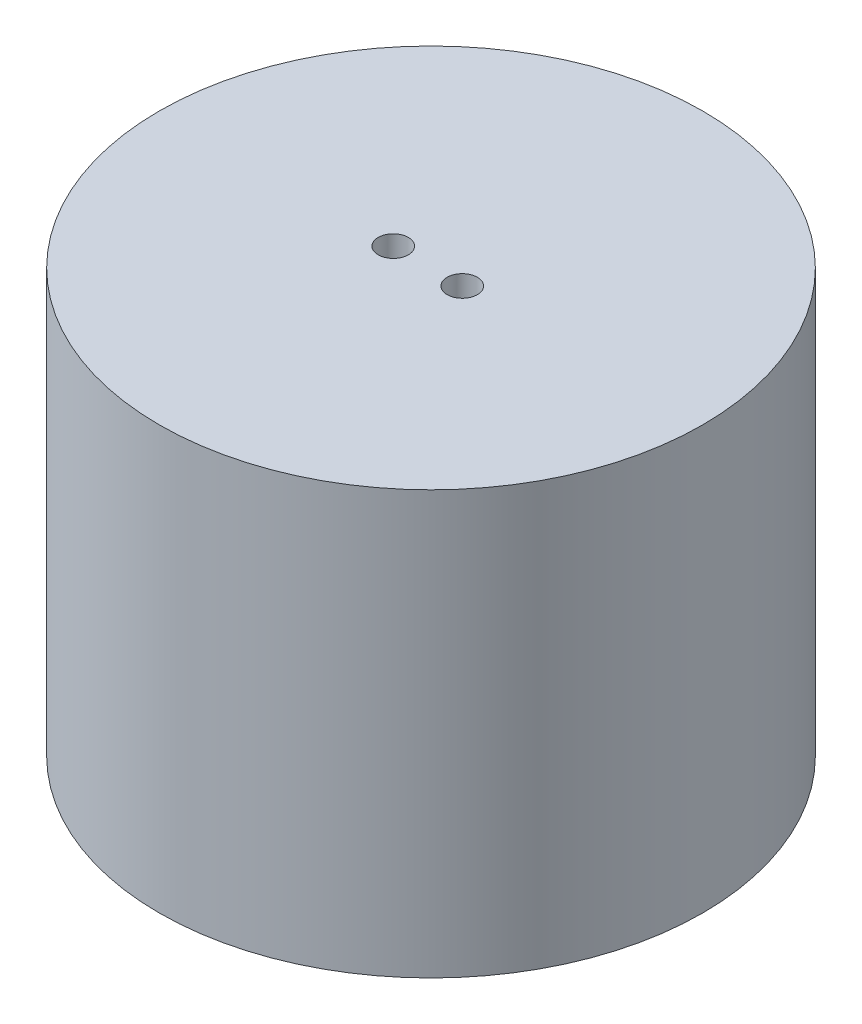
SolidWorks part; units mm, degrees
ref_plane "Front Plane" through (0, 0, 0) normal (0, 0, 1) x (1, 0, 0)
ref_plane "Top Plane" through (0, 0, 0) normal (0, 1, 0) x (1, 0, 0)
ref_plane "Right Plane" through (0, 0, 0) normal (1, 0, 0) x (0, 0, -1)
sketch "Sketch1" plane through (0, 0, 0) normal (0, 1, 0) x (1, 0, 0)
  circle A0 centre (0, 0) radius 7.75
  circle A1 centre (0, 0) radius 9
extrude "Boss-Extrude1" add sketch "Sketch1" along normal blind 4
sketch "Sketch2" plane through (0, 4, 0) normal (0, 1, 0) x (1, 0, 0)
  circle A0 centre (0, 0) radius 9
  circle A1 centre (0, 0) radius 6
extrude "Boss-Extrude2" add sketch "Sketch2" along normal blind 9
thread "Thread2" pitch 1 method cut trim with start face yes trim with end face yes profile "Thread Profile2" start angle 0, offset 1, length 0, pitch 1, diameter 15.5
ref_plane "Plane2" through (7.75, -1, 0) normal (0, 0, 1) x (1, 0, 0)
sketch "Thread Profile2" plane through (7.75, -1, 0) normal (0, 0, 1) x (1, 0, 0)
  line L0 (0, 0) -> (0, 1) construction
  line L1 (0, 0) -> (0.5413, 0.3125)
  line L2 (0.5413, 0.3125) -> (0.5413, 0.4375)
  line L3 (0.5413, 0.4375) -> (0, 0.75)
  line L4 (0.5413, 0.375) -> (0, 0.375) construction
  line L11 (0, 0) -> (0, 0.75)
  point P2 (0, 0)
  dimension "Pitch" = 1
  dimension "Profile_Angle" = 60
  dimension "Profile_Land" = 0.125
  dimension "Profile_Height" = 0.5413
sketch "Sketch3" plane through (0, 13, 0) normal (0, 1, 0) x (1, 0, 0)
  line L0 (0, 0) -> (1.0355, 0)
  line L1 (0, 0) -> (-1.25, 0)
  circle A0 centre (0, 0) radius 9
  circle A1 centre (-1.25, 0) radius 0.5
  circle A2 centre (1.0355, 0) radius 0.5
extrude "Boss-Extrude3" add sketch "Sketch3" along normal blind 1
